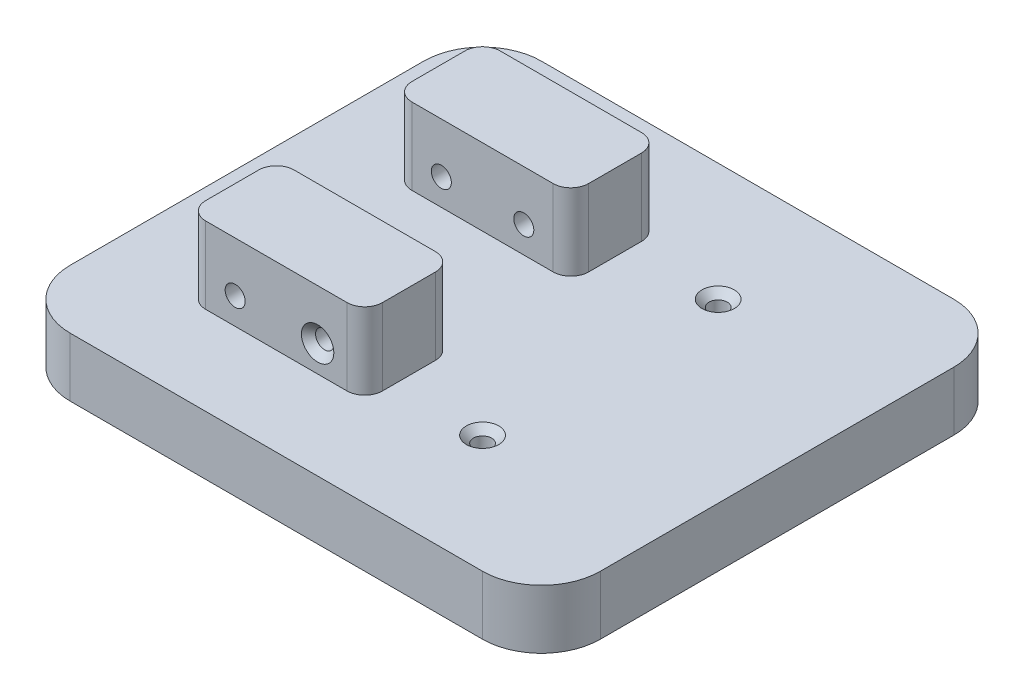
SolidWorks part; units mm, degrees
ref_plane "Piano frontale" through (0, 0, 0) normal (0, 0, 1) x (1, 0, 0)
ref_plane "Piano superiore" through (0, 0, 0) normal (0, 1, 0) x (1, 0, 0)
ref_plane "Piano destro" through (0, 0, 0) normal (1, 0, 0) x (0, 0, -1)
sketch "Schizzo1" plane through (0, 0, 0) normal (0, 1, 0) x (1, 0, 0)
  line L0 (-47.6, 35.6) -> (-47.6, -44.4)
  line L1 (-47.6, 35.6) -> (42.4, 35.6)
  line L2 (42.4, 35.6) -> (42.4, -44.4)
  line L3 (42.4, -44.4) -> (-47.6, -44.4)
  dimension "D1" = 80
  dimension "D2" = 90
extrude "Estrusione-Estrusione1" add sketch "Schizzo1" along normal blind 10
fillet "Raccordo1" radius 10 4 edges at (-47.6, 5, -35.6) (42.4, 5, -35.6) (-47.6, 5, 44.4) (42.4, 5, 44.4)
sketch "Schizzo2" plane through (0, 10, 0) normal (0, 1, 0) x (1, 0, 0)
  line L0 (12.4, -44.4) -> (12.4, 35.6) construction
  line L1 (-37.6, -44.4) -> (32.4, -44.4) construction
  line L2 (32.4, 35.6) -> (-37.6, 35.6) construction
  line L3 (-47.6, 25.6) -> (-47.6, -34.4) construction
  line L4 (12.4, -4.4) -> (-47.6, -4.4) construction
  line L5 (12.4, 15.6) -> (-47.6, 15.6) construction
  line L7 (12.4, -24.4) -> (-47.6, -24.4) construction
  dimension "D1" = 60
  dimension "D2" = 20
  dimension "D3" = 20
hole_wizard "Foro svasato per Vite M2.5-1" positions "Schizzo3D1" profile "Schizzo3" countersink size "M2.5" standard "IS" end condition through all
sketch3d "Schizzo3D1"
  point P0 (12.4, 10, -15.6)
  point P3 (12.4, 10, 24.4)
sketch "Schizzo3" plane through (12.4, 10, -15.6) normal (1, 0, 0) x (0, 0, 1)
  line L0 (0, 0) -> (0, 10)
  line L1 (0, 10) -> (1.55, 10)
  line L2 (1.55, 10) -> (1.55, 1.2)
  line L3 (1.55, 1.2) -> (2.75, 0)
  line L5 (2.75, 0) -> (0, 0)
  line L6 (-1.55, 1.2) -> (-2.75, 0) construction
  line L11 (0, -6.35) -> (0, 107.95) construction
  dimension "Thru Hole Dia." = 3.1
  dimension "Thru Hole Depth" = 10
  dimension "Near C'Sink Dia." = 5.5
  dimension "Near C'Sink Angle" = 90
sketch "Schizzo4" plane through (0, 10, 0) normal (0, 1, 0) x (1, 0, 0)
  line L0 (-32.6, 20.6) -> (-32.6, 5.6)
  line L1 (-32.6, 5.6) -> (-2.6, 5.6)
  line L2 (-2.6, 5.6) -> (-2.6, 20.6)
  line L3 (-2.6, 20.6) -> (-32.6, 20.6)
  line L4 (-2.6, -14.4) -> (-2.6, -29.4)
  line L5 (-2.6, -29.4) -> (-32.6, -29.4)
  line L6 (-32.6, -29.4) -> (-32.6, -14.4)
  line L7 (-32.6, -14.4) -> (-2.6, -14.4)
  line L8 (-47.6, -4.4) -> (42.4, -4.4) construction
  line L10 (-47.6, 25.6) -> (-47.6, -34.4) construction
  line L11 (42.4, -34.4) -> (42.4, 25.6) construction
  dimension "D1" = 15
  dimension "D2" = 15
  dimension "D3" = 10
  dimension "D4" = 10
  dimension "D5" = 15
  dimension "D6" = 30
  dimension "D7" = 30
extrude "Estrusione-Estrusione2" add sketch "Schizzo4" along normal blind 13
sketch "Schizzo5" plane through (0, 0, -20.6) normal (0, 0, -1) x (-1, 0, 0)
  line L0 (32.6, 14.5) -> (2.6, 14.5) construction
  line L1 (2.6, 23) -> (2.6, 10) construction
  line L2 (10.6, 10) -> (10.6, 23) construction
  line L3 (-12.4, 10) -> (47.6, 10) construction
  line L4 (2.6, 23) -> (32.6, 23) construction
  line L6 (24.6, 10) -> (24.6, 23) construction
  line L7 (32.6, 23) -> (32.6, 10) construction
  circle A0 centre (10.6, 14.5) radius 1.7
  circle A1 centre (24.6, 14.5) radius 1.7
  dimension "D4" = 3.4
  dimension "D5" = 3.4
  dimension "D6" = 14
  dimension "D1" = 4.5
  dimension "D2" = 8
  dimension "D3" = 8
sketch "Schizzo6" plane through (0, 0, 29.4) normal (0, 0, 1) x (1, 0, 0)
  line L0 (-32.6, 14.5) -> (-2.6, 14.5) construction
  line L1 (-37.6, 10) -> (32.4, 10) construction
  line L2 (-10.6, 23) -> (-10.6, 10) construction
  line L4 (-24.6, 23) -> (-24.6, 10) construction
  circle A0 centre (-24.6, 14.5) radius 1.7
  dimension "D2" = 3.4
  dimension "D1" = 4.5
hole_wizard "Foro svasato per Vite M2.5-2" positions "Schizzo3D4" profile "Schizzo10" countersink size "M2.5" standard "IS"
sketch3d "Schizzo3D4"
  line L0 (-32.6, 14.5, 29.4) -> (-2.6, 14.5, 29.4) construction
  line L1 (-10.6, 23, 29.4) -> (-10.6, 10, 29.4) construction
  point P0 (-10.6, 14.5, 29.4)
sketch "Schizzo10" plane through (-10.6, 14.5, 29.4) normal (1, 0, 0) x (0, -1, 0)
  line L0 (0, 0) -> (0, 15.9313)
  line L1 (0, 15.9313) -> (1.55, 15)
  line L2 (1.55, 15) -> (1.55, 1.2)
  line L3 (1.55, 1.2) -> (2.75, 0)
  line L5 (2.75, 0) -> (0, 0)
  line L6 (-1.55, 1.2) -> (-2.75, 0) construction
  line L10 (0, 15.9313) -> (-1.55, 15) construction
  line L11 (0, -6.35) -> (0, 107.95) construction
  dimension "Hole Dia." = 3.1
  dimension "Hole Depth" = 15
  dimension "Near C'Sink Dia." = 5.5
  dimension "Near C'Sink Angle" = 90
  dimension "Drill Angle" = 118
fillet "Raccordo2" radius 3 8 edges at (-2.6, 16.5, -20.6) (-2.6, 16.5, -5.6) (-32.6, 16.5, -20.6) (-32.6, 16.5, -5.6) (-2.6, 16.5, 29.4) (-2.6, 16.5, 14.4) (-32.6, 16.5, 14.4) (-32.6, 16.5, 29.4)
extrude "Taglio-Estrusione4" cut sketch "Schizzo5" against normal blind 15
extrude "Taglio-Estrusione5" cut sketch "Schizzo6" against normal blind 15
sketch "Schizzo12" plane through (0, 0, -5.6) normal (0, 0, 1) x (1, 0, 0)
  line L0 (-29.6, 10) -> (-5.6, 10) construction
  line L1 (-24.6, 12.8) -> (-24.6, 10) construction
  line L2 (-17.6, 8.0069) -> (-17.6, 23) construction
  line L3 (-29.6, 23) -> (-5.6, 23) construction
  line L5 (-10.6, 12.8) -> (-10.6, 10) construction
  circle A0 centre (-24.6, 14.5) radius 1.7 construction
  circle A1 centre (-10.6, 14.5) radius 1.7 construction
  dimension "D1" = 14
